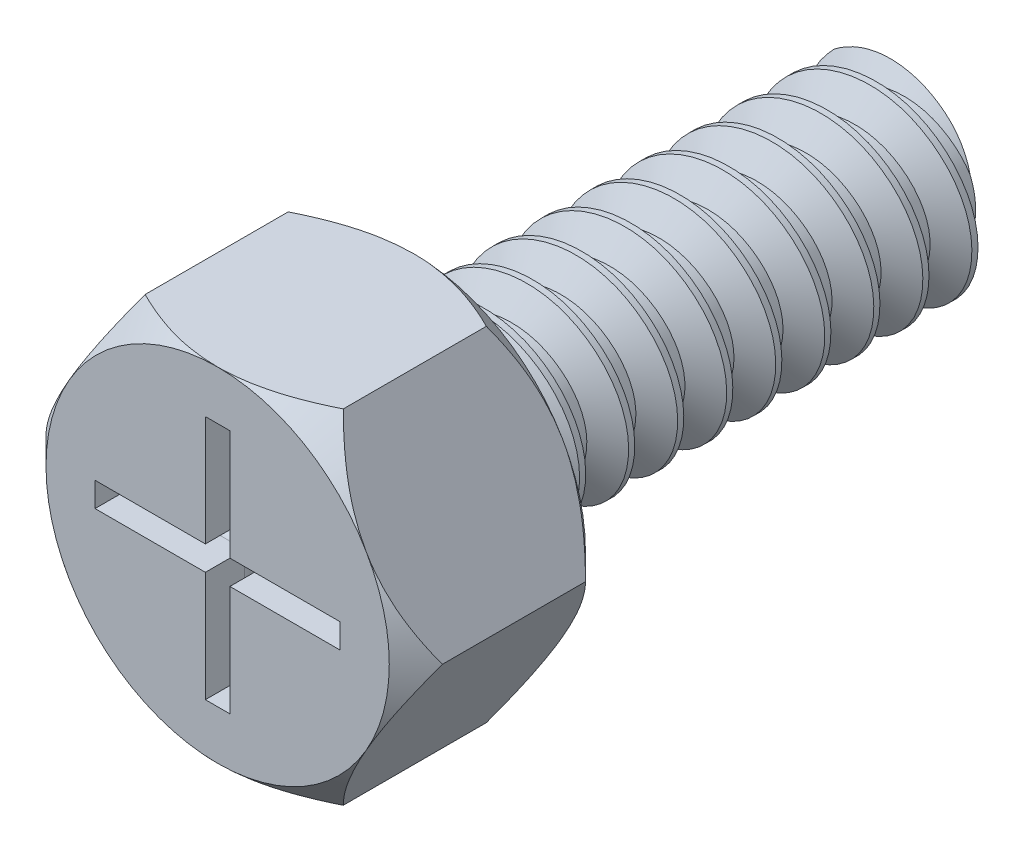
SolidWorks part; units mm, degrees
ref_plane "Front Plane" through (0, 0, 0) normal (0, 0, 1) x (1, 0, 0)
ref_plane "Top Plane" through (0, 0, 0) normal (0, 1, 0) x (1, 0, 0)
ref_plane "Right Plane" through (0, 0, 0) normal (1, 0, 0) x (0, 0, -1)
sketch "Sketch1" plane through (0, 0, 0) normal (0, 0, 1) x (1, 0, 0)
  line L0 (-2.0207, 0) -> (2.0207, 0) construction
  line L1 (2.0207, 0) -> (1.0104, 1.75)
  line L2 (1.0104, 1.75) -> (-1.0104, 1.75)
  line L3 (-1.0104, 1.75) -> (-2.0207, 0)
  line L4 (-2.0207, 0) -> (-1.0104, -1.75)
  line L5 (-1.0104, -1.75) -> (1.0104, -1.75)
  line L6 (1.0104, -1.75) -> (2.0207, 0)
  line L7 (0, 1.75) -> (0, -1.75) construction
  circle A0 centre (0, 0) radius 1.75
  circle A1 centre (0, 0) radius 1
  dimension "D1" = 3.5
  dimension "D2" = 2
extrude "Boss-Extrude1" add sketch "Sketch1" along normal blind 2 contours L1 L2 L3 L4 L5 L6
extrude "Boss-Extrude2" add sketch "Sketch1<3>" along normal up to next (2 mm away) and the other way blind 5 contours A1
sketch "Sketch1<3>" plane through (0, 0, 0) normal (0, 0, 1) x (1, 0, 0) same geometry as "Sketch1"
thread "Thread1" pitch 0.5 method cut profile "Thread Profile2" start angle 0, offset 0, length 0, pitch 0.5, diameter 2
ref_plane "Plane2" through (-1, 0, 0) normal (0, -1, 0) x (-1, 0, 0)
sketch "Thread Profile2" plane through (-1, 0, 0) normal (0, -1, 0) x (-1, 0, 0)
  line L0 (0, 0) -> (0, 0.5) construction
  line L11 (0, 0) -> (0, 0.4375)
  line L12 (0, 0.4375) -> (-0.2706, 0.2812)
  line L13 (-0.2706, 0.2812) -> (-0.2706, 0.1562)
  line L15 (-0.2706, 0.1562) -> (0, 0)
  line L17 (-0.2706, 0.2187) -> (0, 0.2187) construction
  point P2 (0, 0)
  dimension "Pitch" = 0.5
  dimension "Profile_Angle" = 60
  dimension "Profile_Land" = 0.125
  dimension "Profile_Height" = 0.2706
extrude "Cut-Extrude3" cut sketch "Sketch1<8>" along normal blind 1 draft 45 flip side to cut contours A0
sketch "Sketch1<8>" plane through (0, 0, 0) normal (0, 0, 1) x (1, 0, 0) same geometry as "Sketch1"
ref_plane "Plane3" through (0, 0, 2) normal (0, 0, 1) x (1, 0, 0)
sketch "Sketch8" plane through (0, 0, 2) normal (0, 0, 1) x (1, 0, 0)
  circle A0 centre (0, 0) radius 1.75
  dimension "D1" = 3.5
extrude "Cut-Extrude4" cut sketch "Sketch8" against normal blind 1 draft 45 flip side to cut contours A0
ref_plane "Plane4" through (0, 0, -5) normal (0, 0, -1) x (-1, 0, 0)
sketch "Sketch9" plane through (0, 0, -5) normal (0, 0, -1) x (-1, 0, 0)
  line L0 (-2.0207, 0) -> (2.0207, 0) construction
  line L1 (0, 1.75) -> (0, -1.75) construction
  line L2 (-1.0104, 1.75) -> (1.0104, 1.75) construction
ref_plane "Plane5" through (0, 0, 2) normal (0, 0, 1) x (1, 0, 0)
sketch "Sketch10" plane through (0, 0, 2) normal (0, 0, 1) x (1, 0, 0)
  line L0 (0, 1.25) -> (0, -1.25) construction
  line L1 (1.25, 0) -> (-1.25, 0) construction
  line L2 (-0.125, -1.25) -> (0.125, -1.25)
  line L3 (0.125, -1.25) -> (0.125, -0.125)
  line L4 (0.125, -0.125) -> (1.25, -0.125)
  line L5 (1.25, -0.125) -> (1.25, 0.125)
  line L6 (1.25, 0.125) -> (0.125, 0.125)
  line L7 (0.125, 0.125) -> (0.125, 1.25)
  line L8 (0.125, 1.25) -> (-0.125, 1.25)
  line L9 (-0.125, 1.25) -> (-0.125, 0.125)
  line L10 (-0.125, 0.125) -> (-1.25, 0.125)
  line L12 (-1.25, 0.125) -> (-1.25, -0.125)
  line L13 (-1.25, -0.125) -> (-0.125, -0.125)
  line L14 (-0.125, -0.125) -> (-0.125, -1.25)
  point P5 (0, 0)
  point P10 (0, 0)
  dimension "D1" = 2.5
  dimension "D2" = 2.5
  dimension "D3" = 0.25
  dimension "D4" = 0.25
  dimension "D5" = 0.25
  dimension "D6" = 0.25
  dimension "D7" = 0.25
  dimension "D8" = 1.125
  dimension "D9" = 1.125
  dimension "D10" = 1.125
extrude "Cut-Extrude5" cut sketch "Sketch10" against normal blind 0.5
fillet "Fillet1" radius 0.1 12 edges at (-0.6875, -0.125, 1.5) (-1.25, 0, 1.5) (-0.6875, 0.125, 1.5) (-0.125, 0.6875, 1.5) (0, 1.25, 1.5) (0.125, 0.6875, 1.5) (0.6875, 0.125, 1.5) (1.25, 0, 1.5) (0.6875, -0.125, 1.5) (0.125, -0.6875, 1.5) (0, -1.25, 1.5) (-0.125, -0.6875, 1.5)
equation "\"D1@Sketch8\"= \"D1@Sketch1\""
